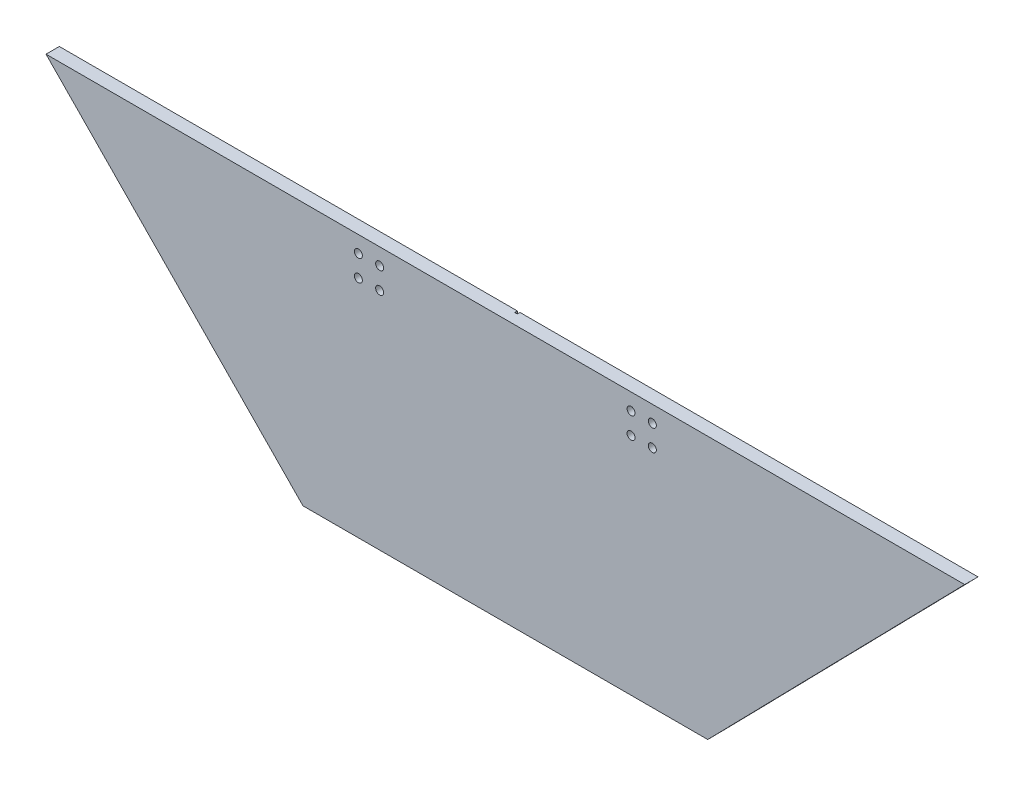
SolidWorks part; units mm, degrees
ref_plane "前视基准面" through (0, 0, 0) normal (0, 0, 1) x (1, 0, 0)
ref_plane "上视基准面" through (0, 0, 0) normal (0, 1, 0) x (1, 0, 0)
ref_plane "右视基准面" through (0, 0, 0) normal (1, 0, 0) x (0, 0, -1)
sketch "草图1" plane through (0, 0, 0) normal (0, 0, 1) x (1, 0, 0)
  line L0 (-172.5, 0) -> (172.5, 0)
  line L1 (172.5, 0) -> (76, -98.6496)
  line L2 (0, 0) -> (0, -197.2993) construction
  line L3 (76, -98.6496) -> (-76, -98.6496)
  line L4 (-172.5, 0) -> (-76, -98.6496)
  point P8 (0, -98.6496)
  dimension "D1" = 345
  dimension "D4" = 138
  dimension "D5" = 152
extrude "凸台-拉伸1" add sketch "草图1" along normal blind 5
sketch "草图3" plane through (0, 0, 0) normal (0, 0, -1) x (-1, 0, 0)
  line L0 (0, 78.8943) -> (0, -217.9421) construction
  line L6 (-0.5, 62.2351) -> (0.5, 62.2351)
  line L7 (-0.5, 62.2351) -> (-0.5, -161.9066)
  line L8 (-0.5, -161.9066) -> (0.5, -161.9066)
  line L9 (0.5, 62.2351) -> (0.5, -161.9066)
  line L10 (-0.5, 62.2351) -> (0.5, -161.9066) construction
  line L11 (-0.5, -161.9066) -> (0.5, 62.2351) construction
  point P2 (0, -49.8357)
  dimension "D1" = 1
extrude "切除-拉伸2" cut sketch "草图3" against normal blind 1
fillet "圆角1" radius 10 1 edges at (-38.25, -98.6496, 0)
sketch "草图7" plane through (0, 0, 0) normal (0, 0, -1) x (-1, 0, 0)
  circle A0 centre (55.2, -14.1747) radius 1.5 construction
  circle A1 centre (47.2, -14.1747) radius 1.5 construction
  circle A2 centre (47.2, -6.1747) radius 1.5 construction
  circle A3 centre (55.2, -6.1747) radius 1.5 construction
  circle A4 centre (-55.2, -6.1747) radius 1.5 construction
  circle A5 centre (-55.2, -14.1747) radius 1.5 construction
  circle A6 centre (-47.2, -14.1747) radius 1.5 construction
  circle A7 centre (-47.2, -6.1747) radius 1.5 construction
  circle A8 centre (55.2, -14.1747) radius 1.5
  circle A9 centre (47.2, -14.1747) radius 1.5
  circle A10 centre (47.2, -6.1747) radius 1.5
  circle A11 centre (55.2, -6.1747) radius 1.5
  circle A12 centre (-55.2, -6.1747) radius 1.5
  circle A13 centre (-55.2, -14.1747) radius 1.5
  circle A14 centre (-47.2, -14.1747) radius 1.5
  circle A15 centre (-47.2, -6.1747) radius 1.5
extrude "切除-拉伸3" cut sketch "草图7" against normal blind 10
